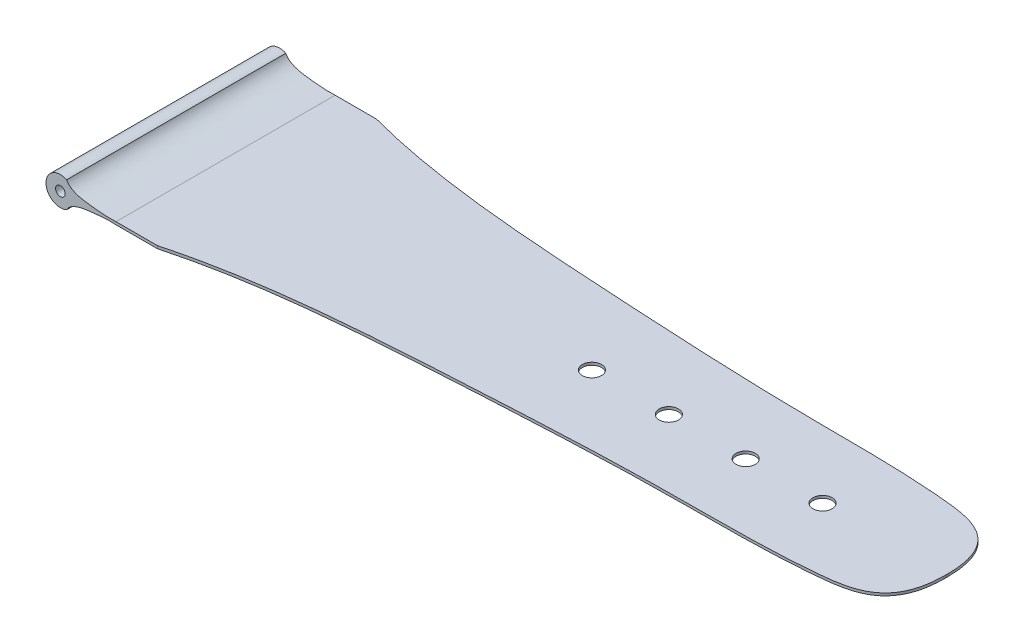
SolidWorks part; units mm, degrees
material "Plastique personnalisé"
ref_plane "Plan de face" through (0, 0, 0) normal (0, 0, 1) x (1, 0, 0)
ref_plane "Plan de dessus" through (0, 0, 0) normal (0, 1, 0) x (1, 0, 0)
ref_plane "Plan de droite" through (0, 0, 0) normal (1, 0, 0) x (0, 0, -1)
sketch "Esquisse2" plane through (0, 0, 0) normal (0, 0, 1) x (1, 0, 0)
  line L0 (5.7911, 0.1421) -> (80.7911, 0.1332)
  line L1 (0, 0) -> (12.6201, 0) construction
  line L2 (5.7911, -0.1421) -> (80.7911, -0.1332)
  arc A0 (0.6509, 1.3514) -> (0.6509, -1.3514) centre (0, 0) ccw
  circle A1 centre (0, 0) radius 0.5
  arc A2 (80.7911, 0.1332) -> (80.7911, -0.1332) centre (20.6774, 0) cw
  spline S0 degree 3 poles (0.6509, 1.3514) (1.1145, 0.5104) (3.0699, 0.2682) (5.0293, 0.0873) (5.7911, 0.1421) knots 0 0 0 0 0.614721 1 1 1 1
  spline S1 degree 3 poles (0.6509, -1.3514) (1.1145, -0.5104) (3.0699, -0.2682) (5.0293, -0.0873) (5.7911, -0.1421) knots 0 0 0 0 0.614721 1 1 1 1
  dimension "D1" = 3
  dimension "D2" = 1
  dimension "D3" = 75
extrude "Boss.-Extru.1" add sketch "Esquisse2" along normal blind 11.4 and the other way blind 11.4
sketch "Esquisse3" plane through (0, 0.1427, 0) normal (0.0001, 1, 0) x (1, -0.0001, 0)
  line L0 (80.791, 11.4) -> (5.791, 11.4) construction
  line L1 (80.791, 0) -> (91.4532, 0) construction
  line L2 (80.791, 11.4) -> (80.791, -11.4) construction
  line L3 (10.1022, -11.4) -> (10.1022, -17.0991)
  line L4 (10.1022, -17.0991) -> (86.3445, -17.0991)
  line L5 (86.3445, -17.0991) -> (86.3445, 15.2707)
  line L6 (86.3445, 15.2707) -> (10.1022, 15.2707)
  line L7 (10.1022, 15.2707) -> (10.1022, 11.4)
  spline S0 degree 3 poles (10.1022, 11.4) (17.188, 9.5059) (27.8071, 8.4741) (44.0211, 7.5455) (58.1053, 6.872) (72.1431, 7.1647) (80.8398, 5.7025) (80.791, 0) knots 0 0 0 0 0.295599 0.428617 0.65643 0.863094 1 1 1 1
  spline S1 degree 3 poles (10.1022, -11.4) (17.188, -9.5059) (27.8071, -8.4741) (44.0211, -7.5455) (58.1053, -6.872) (72.1431, -7.1647) (80.8398, -5.7025) (80.791, 0) knots 0 0 0 0 0.295599 0.428617 0.65643 0.863094 1 1 1 1
extrude "Enlèv. mat.-Extru.1" cut sketch "Esquisse3" against normal through all both and the other way through all
sketch "Esquisse4" plane through (0, 0.1427, 0) normal (0.0001, 1, 0) x (1, -0.0001, 0)
  circle A0 centre (67.918, 0) radius 1
  circle A1 centre (59.918, 0) radius 1
  circle A2 centre (51.918, 0) radius 1
  circle A3 centre (43.918, 0) radius 1
  dimension "D1" = 4
extrude "Enlèv. mat.-Extru.2" cut sketch "Esquisse4" against normal blind 10
